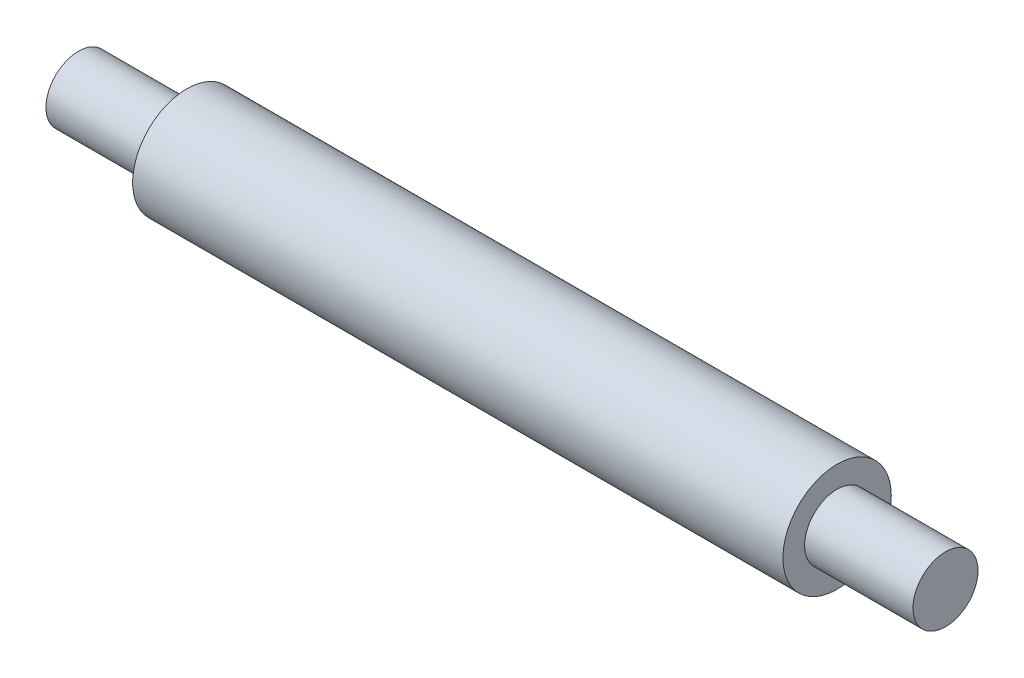
SolidWorks part; units mm, degrees
ref_plane "Front Plane" through (0, 0, 0) normal (0, 0, 1) x (1, 0, 0)
ref_plane "Top Plane" through (0, 0, 0) normal (0, 1, 0) x (1, 0, 0)
ref_plane "Right Plane" through (0, 0, 0) normal (1, 0, 0) x (0, 0, -1)
sketch "Sketch1" plane through (0, 0, 0) normal (1, 0, 0) x (0, 0, -1)
  circle A0 centre (0, 0) radius 5
  dimension "D1" = 10
extrude "Boss-Extrude1" add sketch "Sketch1" along normal blind 30 and the other way blind 30
sketch "Sketch2" plane through (30, 0, 0) normal (1, 0, 0) x (0, 0, -1)
  circle A0 centre (0, 0) radius 3
  dimension "D1" = 6
extrude "Boss-Extrude2" add sketch "Sketch2" along normal blind 10
mirror "Mirror1" about plane through (0, 0, 0) normal (1, 0, 0) of "Boss-Extrude2"
